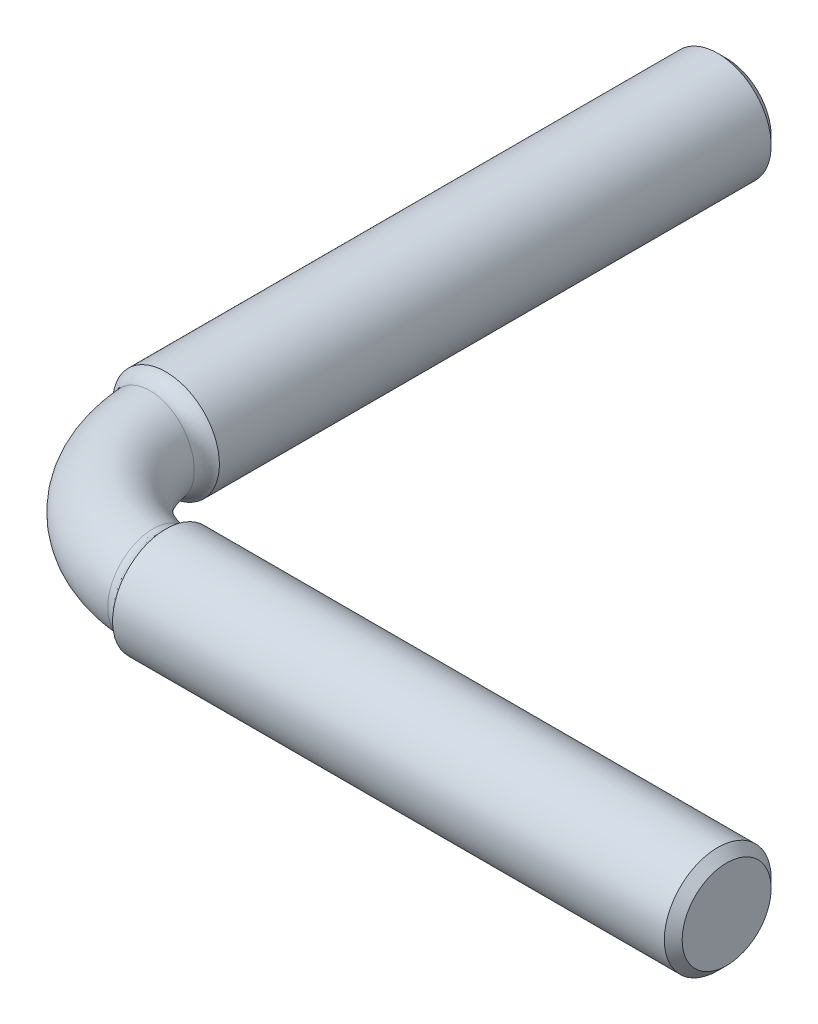
SolidWorks part; units mm, degrees
ref_plane "Front Plane" through (0, 0, 0) normal (0, 0, 1) x (1, 0, 0)
ref_plane "Top Plane" through (0, 0, 0) normal (0, 1, 0) x (1, 0, 0)
ref_plane "Right Plane" through (0, 0, 0) normal (1, 0, 0) x (0, 0, -1)
sketch "Sketch1" plane through (0, 0, 0) normal (0, 1, 0) x (1, 0, 0)
  line L0 (0, 31.5) -> (0, 0)
  line L1 (7.6394, -7.6394) -> (39.1394, -7.6394)
  arc A0 (0, 0) -> (7.6394, -7.6394) centre (7.6394, 0) ccw
  dimension "D2" = 75
  dimension "D1" = 31.5
sweep "Sweep1" add path "Sketch1" circular profile diameter 5 parameters "D3"=5
sketch "Sketch8" plane through (0, 0, -31.5) normal (0, 0, -1) x (-1, 0, 0)
  circle A0 centre (0, 0) radius 3
  dimension "D1" = 6
extrude "Boss-Extrude1" add sketch "Sketch8" against normal blind 31.5
sketch "Sketch9" plane through (39.1394, 0, 0) normal (1, 0, 0) x (0, 0, -1)
  circle A0 centre (-7.6394, 0) radius 3
  dimension "D1" = 6
extrude "Boss-Extrude2" add sketch "Sketch9" against normal blind 31.5
chamfer "Chamfer1" distance 0.5 angle 45 1 edges at (39.1394, 0, 4.6394)
chamfer "Chamfer2" distance 0.5 angle 45 1 edges at (-3, 0, -31.5)
fillet "Fillet1" radius 1 1 edges at (-2.5, 0, 0)
fillet "Fillet2" radius 1 1 edges at (7.6394, 0, 5.1394)
